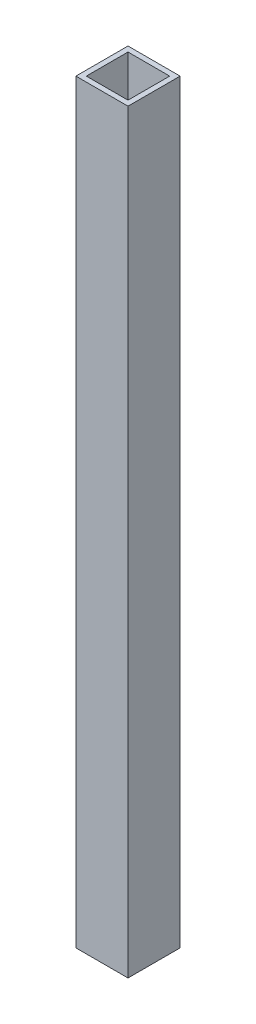
SolidWorks part; units mm, degrees
material "6061 Alloy"
ref_plane "Front Plane" through (0, 0, 0) normal (0, 0, 1) x (1, 0, 0)
ref_plane "Top Plane" through (0, 0, 0) normal (0, 1, 0) x (1, 0, 0)
ref_plane "Right Plane" through (0, 0, 0) normal (1, 0, 0) x (0, 0, -1)
sketch "Sketch1" plane through (0, 0, 0) normal (0, 1, 0) x (1, 0, 0)
  line L1 (0, 0) -> (15, 0)
  line L2 (0, 0) -> (0, 15)
  line L3 (0, 15) -> (15, 15)
  line L4 (15, 0) -> (15, 15)
  dimension "D1" = 15
extrude "Extrude-Thin1" add sketch "Sketch1" along normal blind 217.3 thin thin type one direction reverse wall 1.5
